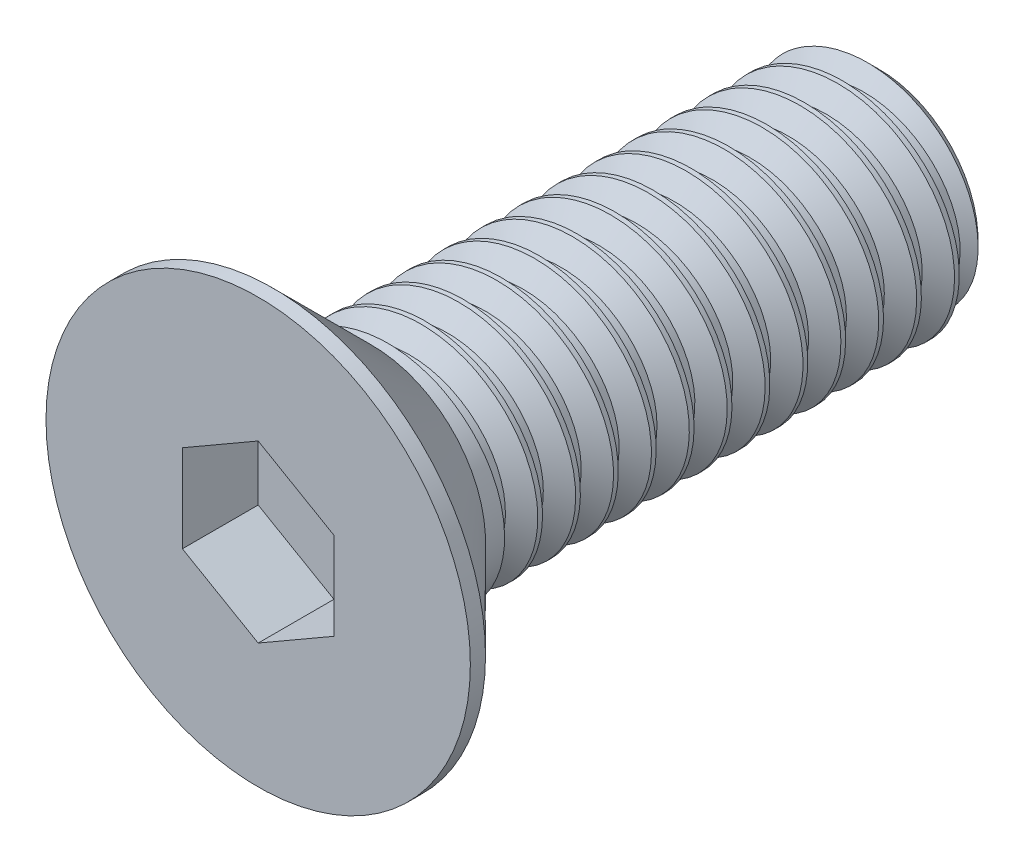
SolidWorks part; units mm, degrees
material "Alloy Steel"
ref_plane "Front Plane" through (0, 0, 0) normal (1, 0, 0) x (0, 1, 0)
ref_plane "Top Plane" through (0, 0, 0) normal (0, 0, 1) x (0, 1, 0)
ref_plane "Right Plane" through (0, 0, 0) normal (0, 1, 0) x (-1, 0, 0)
ref_axis "x axis" through (-88.99, 0, 0) along (1, 0, 0)
ref_axis "y xxis" through (0, 88.99, 0) along (0, -1, 0)
ref_axis "z axis" through (0, 0, 55) along (0, 0, -1)
sketch "Sketch2" plane through (0, 0, 0) normal (1, 0, 0) x (0, 1, 0)
  line L0 (0, 0) -> (2.8, 0)
  line L1 (2.8, 0) -> (2.8, -0.2)
  line L2 (2.8, -0.2) -> (1.5, -1.5)
  line L3 (1.5, -1.5) -> (1.5, -8)
  line L5 (0, -8) -> (0, 0)
  line L6 (1.5, -8) -> (1.3, -8.2)
  line L7 (1.3, -8.2) -> (0, -8.2)
  line L8 (0, -8.2) -> (0, -8)
  line L9 (0, -8) -> (1.5, -8) construction
  dimension "D1" = 1.5
  dimension "D2" = 45
  dimension "D3" = 0.2
  dimension "D4" = 2.8
  dimension "D5" = 45
  dimension "D6" = 0.2
  dimension "D7" = 8.2
revolve "Revolve1" add sketch "Sketch2" angle 360 about L5
sketch "Sketch3" plane through (0, 0, 0) normal (0, 0, 1) x (1, 0, 0)
  line L1 (1, 0.5774) -> (0, 1.1547)
  line L2 (0, 1.1547) -> (-1, 0.5774)
  line L3 (-1, 0.5774) -> (-1, -0.5774)
  line L4 (-1, -0.5774) -> (0, -1.1547)
  line L5 (0, -1.1547) -> (1, -0.5774)
  line L6 (1, -0.5774) -> (1, 0.5774)
  circle A0 centre (0, 0) radius 1 construction
  dimension "D1" = 2
extrude "Cut-Extrude1" cut sketch "Sketch3" against normal blind 1
thread "Thread1" pitch 0.5 method cut profile "Thread Profile1" start angle 0, offset 0, length 0, pitch 0.5, diameter 3
ref_plane "Plane1" through (-1.5, 0, -1.5) normal (0, -1, 0) x (-1, 0, 0)
sketch "Thread Profile1" plane through (-1.5, 0, -1.5) normal (0, -1, 0) x (-1, 0, 0)
  line L0 (0, 0) -> (0, 0.5) construction
  line L11 (0, 0) -> (0, 0.4375)
  line L12 (0, 0.4375) -> (-0.2706, 0.2812)
  line L13 (-0.2706, 0.2812) -> (-0.2706, 0.1562)
  line L15 (-0.2706, 0.1562) -> (0, 0)
  line L17 (-0.2706, 0.2187) -> (0, 0.2187) construction
  point P2 (0, 0)
  dimension "Pitch" = 0.5
  dimension "Profile_Angle" = 60
  dimension "Profile_Land" = 0.125
  dimension "Profile_Height" = 0.2706
